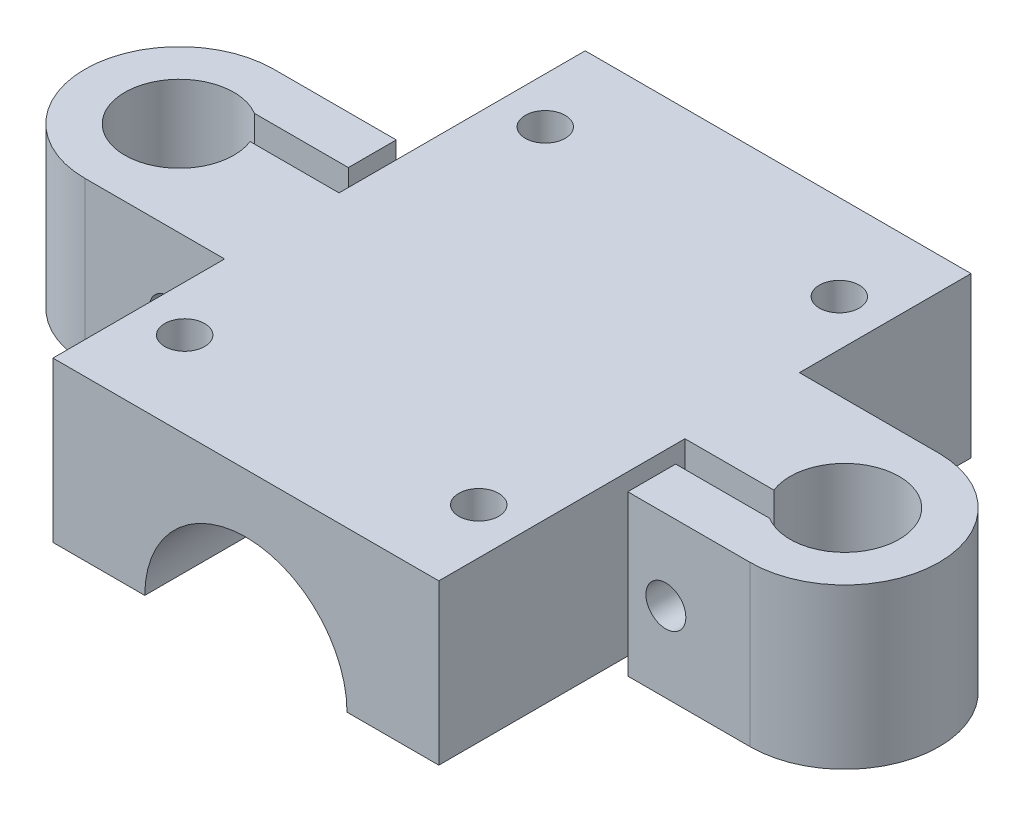
SolidWorks part; units mm, degrees
material "ABS"
ref_plane "Front Plane" through (0, 0, 0) normal (1, 0, 0) x (0, 1, 0)
ref_plane "Top Plane" through (0, 0, 0) normal (0, 0, 1) x (0, 1, 0)
ref_plane "Right Plane" through (0, 0, 0) normal (0, 1, 0) x (-1, 0, 0)
sketch "Sketch1" plane through (0, 0, 0) normal (0, 0, 1) x (0, 1, 0)
  line L0 (0, -6.9) -> (0, -14.5) construction
  line L1 (0, 0) -> (12, 0)
  line L2 (0, 0) -> (0, -6.9)
  line L3 (0, -29) -> (12, -29)
  line L4 (12, 0) -> (12, -29)
  line L5 (6, -29) -> (6, 0) construction
  line L6 (0, -14.5) -> (12, -14.5) construction
  line L7 (0, -22.1) -> (0, -29)
  line L8 (0, -14.5) -> (0, -22.1) construction
  arc A0 (0, -22.1) -> (0, -6.9) centre (0, -14.5) ccw
  arc A1 (0, -6.9) -> (0, -22.1) centre (0, -14.5) ccw construction
  point P428 (6, -14.5)
  dimension "D3" = 15.2
  dimension "D1" = 29
  dimension "D2" = 12
extrude "Boss-Extrude1" add sketch "Sketch1" along normal blind 20 and the other way blind 20 contours A0 L7 L3 L4 L1 L2 region at (0.3138, 6, 0)
sketch "Sketch3" plane through (0, 12, 0) normal (0, 1, 0) x (-1, 0, 0)
  line L0 (0, 0) -> (-29, 0) construction
  line L1 (0, -20) -> (0, 20) construction
  line L2 (-29, -20) -> (-29, 20) construction
  line L3 (10.5, 0) -> (-39.5, 0) construction
  line L4 (10.5, -7.1) -> (-39.5, -7.1)
  line L5 (10.5, 7.1) -> (-39.5, 7.1)
  line L6 (-14.5, 20) -> (-14.5, -20) construction
  line L7 (0, 20) -> (-29, 20) construction
  line L8 (0, -20) -> (-29, -20) construction
  line L9 (1.3, -7.1) -> (1.3, -3.5)
  line L10 (1.3, -3.5) -> (8.3646, -3.5)
  line L11 (6.6842, -1.5) -> (0, -1.5)
  line L12 (0, -1.5) -> (0, -7.1)
  line L13 (0, -7.1) -> (1.3, -7.1)
  line L14 (-30.3, 7.1) -> (-30.3, 3.5)
  line L15 (-30.3, 3.5) -> (-37.3646, 3.5)
  line L16 (-35.6842, 1.5) -> (-29, 1.5)
  line L17 (-29, 1.5) -> (-29, 7.1)
  line L18 (-29, 7.1) -> (-30.3, 7.1)
  arc A0 (10.5, -7.1) -> (10.5, 7.1) centre (10.5, 0) ccw
  arc A1 (-39.5, 7.1) -> (-39.5, -7.1) centre (-39.5, 0) ccw
  arc A2 (-37.3646, 3.5) -> (-35.6842, 1.5) centre (-39.5, 0) ccw
  arc A3 (8.3646, -3.5) -> (6.6842, -1.5) centre (10.5, 0) ccw
  arc A4 (6.6842, -1.5) -> (8.3646, -3.5) centre (10.5, 0) ccw construction
  arc A5 (-35.6842, 1.5) -> (-37.3646, 3.5) centre (-39.5, 0) ccw construction
  point P9 (-14.5, 0)
  point P22 (-14.5, 0)
  line M6 (0, -20) -> (0, 20)
  line M8 (-29, 20) -> (-29, -20)
  dimension "D3" = 8.2
  dimension "D4" = 50
  dimension "D5" = 2
  dimension "D7" = 1.5
  dimension "D8" = 1.3
  dimension "D9" = 2
  dimension "D10" = 1.5
extrude "Boss-Extrude2" add sketch "Sketch3" against normal up to surface (12 mm away) contours A3 L10 L9 L4 A0 L5 L11 M6 | A2 L15 L14 L5 A1 L4 L16 M8 region at (-5.9, 12, -6.8739) region at (34.25, 12, -6.8739) up to face at (3.45, 0, 0)
sketch "Sketch4" plane through (0, 0, -1.5) normal (0, 0, -1) x (1, 0, 0)
  line L0 (-6.6842, -6) -> (0, -6) construction
  line L1 (-6.6842, 0) -> (-6.6842, -12) construction
  circle A0 centre (-4.1642, -6) radius 1.5
  dimension "screw_hole" = 3
  dimension "D1" = 2.52
extrude "Cut-Extrude1" cut sketch "Sketch4" against normal through all and the other way through all contours A0 L0 | L0 A0 region at (-4.1642, 5.3634, -1.5) region at (-4.1642, 6.6366, -1.5)
sketch "Sketch5" plane through (0, 0, 1.5) normal (0, 0, 1) x (1, 0, 0)
  line L0 (35.6842, 6) -> (29, 6) construction
  line L1 (35.6842, 0) -> (35.6842, 12) construction
  line L2 (29, 0) -> (29, 12) construction
  circle A0 centre (33.1642, 6) radius 1.5
  dimension "D2" = 2.52
extrude "Cut-Extrude2" cut sketch "Sketch5" against normal through all and the other way through all contours L0 A0 | A0 L0 region at (33.1642, 5.3634, 1.5) region at (33.1642, 6.6366, 1.5)
sketch "Sketch7" plane through (0, 0, 0) normal (0, -1, 0) x (1, 0, 0)
  line L0 (0, 20) -> (6.9, 7.1) construction
  line L1 (6.9, -20) -> (6.9, 20) construction
  line L2 (0, 7.1) -> (6.9, 20) construction
  line L3 (29, -7.1) -> (22.1, -20) construction
  line L4 (29, -20) -> (22.1, -7.1) construction
  line L5 (22.1, -20) -> (22.1, 20) construction
  line L6 (0, -20) -> (6.9, -7.1) construction
  line L7 (6.9, -20) -> (0, -7.1) construction
  line L9 (22.1, 20) -> (29, 7.1) construction
  line L10 (29, 1.5) -> (29, 20) construction
  line L11 (29, 20) -> (22.1, 7.1) construction
  line L12 (0, -20) -> (0, -1.5) construction
  circle A0 centre (3.45, 13.55) radius 1.5
  circle A1 centre (25.55, -13.55) radius 1.5
  circle A2 centre (25.55, 13.55) radius 1.5
  circle A3 centre (3.45, -13.55) radius 1.5
  dimension "D3" = 12.9
  dimension "D4" = 12.9
  dimension "x_hole_offset" = 12.9
  dimension "D6" = 12.9
extrude "Cut-Extrude3" cut sketch "Sketch7" against normal through all
equation "\"D2@Sketch3\"=\"D1@Sketch3\""
equation "\"D8@Sketch3\"=\"D6@Sketch3\""
equation "\"D9@Sketch3\"=\"D5@Sketch3\""
equation "\"D10@Sketch3\"=\"D7@Sketch3\""
equation "\"screw_hole\"= 3mm"
equation "\"offset\"= 2.52mm"
equation "\"screw_hole@Sketch4\"=\"screw_hole\""
equation "\"D1@Sketch4\"=\"offset\""
equation "\"D1@Sketch5\"=\"screw_hole\""
equation "\"D2@Sketch5\"=\"offset\""
equation "\"D1@Sketch7\"=\"screw_hole\""
equation "\"D4@Sketch7\"=\"D3@Sketch7\""
equation "\"y_length\" = 40mm"
equation "\"z_breadth\"= 29mm"
equation "\"D1@Boss-Extrude1\"=\"y_length\"/2"
equation "\"D2@Boss-Extrude1\"=\"y_length\"/2"
equation "\"D1@Sketch1\"=\"z_breadth\""
equation "\"lm8uu_bearing_dia\"= 15.2mm"
equation "\"D3@Sketch1\"= \"lm8uu_bearing_dia\""
equation "\"x_steel_rods_gap\"= 50mm"
equation "\"D4@Sketch3\"=\"x_steel_rods_gap\""
